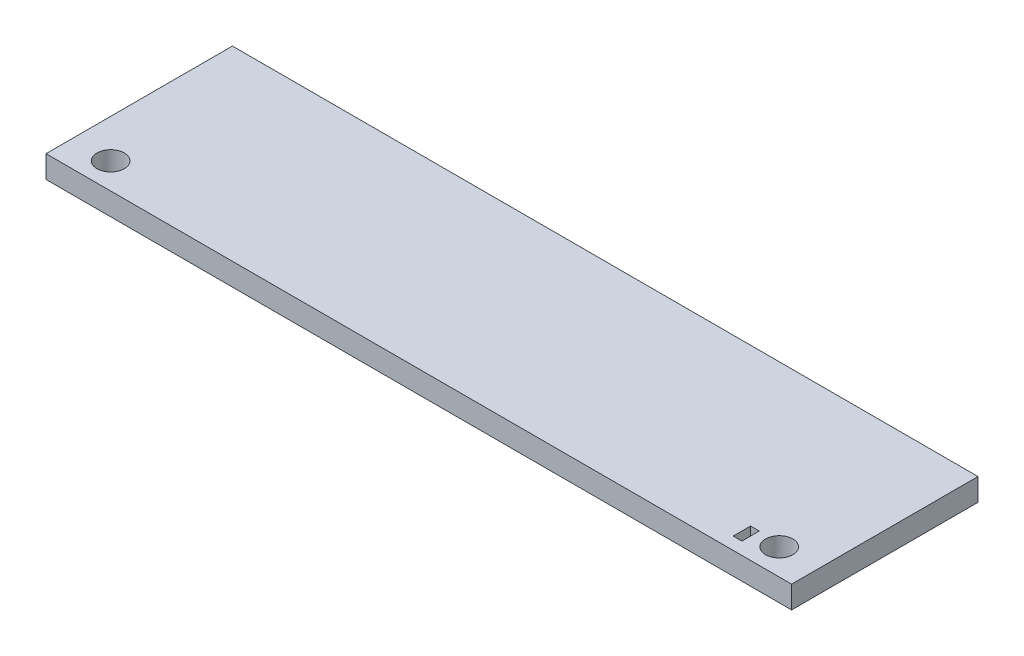
SolidWorks part; units mm, degrees
ref_plane "Plan de face" through (0, 0, 0) normal (0, 0, 1) x (1, 0, 0)
ref_plane "Plan de dessus" through (0, 0, 0) normal (0, 1, 0) x (1, 0, 0)
ref_plane "Plan de droite" through (0, 0, 0) normal (1, 0, 0) x (0, 0, -1)
sketch "Esquisse1" plane through (0, 0, 0) normal (0, 1, 0) x (1, 0, 0)
  line L1 (-300, 75) -> (300, 75)
  line L2 (-300, 75) -> (-300, -75)
  line L3 (-300, -75) -> (300, -75)
  line L4 (300, 75) -> (300, -75)
  line L5 (-300, 75) -> (300, -75) construction
  line L6 (-300, -75) -> (300, 75) construction
  point P0 (0, 0)
  dimension "D1" = 600
  dimension "D2" = 150
extrude "Boss.-Extru.1" add sketch "Esquisse1" along normal blind 18
sketch "Esquisse2" plane through (0, 18, 0) normal (0, 1, 0) x (1, 0, 0)
  line L0 (-300, 75) -> (-300, -75) construction
  line L1 (-300, 55) -> (300, 55)
  line L2 (-300, 55) -> (-300, 35)
  line L3 (-300, 35) -> (300, 35)
  line L4 (300, 55) -> (300, 35)
  line L5 (300, -75) -> (300, 75) construction
  line L6 (300, 75) -> (-300, 75) construction
  dimension "D1" = 20
  dimension "D2" = 20
sketch "Esquisse3" plane through (0, 18, 0) normal (0, 1, 0) x (1, 0, 0)
  line L0 (-238, -75) -> (-238, -33) construction
  line L1 (-300, -75) -> (300, -75) construction
  line L2 (-238, -33) -> (-300, -33) construction
  line L3 (-300, 75) -> (-300, -75) construction
  line L4 (238, -75) -> (238, -33) construction
  line L5 (238, -33) -> (300, -33) construction
  line L6 (300, -75) -> (300, 75) construction
  line L7 (238, -33) -> (300, -75) construction
  line L8 (-238, -33) -> (-300, -75) construction
  circle A0 centre (269, -54) radius 11
  circle A1 centre (-269, -54) radius 11
  dimension "D5" = 22
  dimension "D6" = 22
  dimension "D1" = 62
  dimension "D2" = 42
  dimension "D3" = 62
  dimension "D4" = 42
extrude "Enlèv. mat.-Extru.1" cut sketch "Esquisse3" against normal blind 20
sketch "Esquisse4" plane through (0, 18, 0) normal (0, 1, 0) x (1, 0, 0)
  line L0 (300, -75) -> (300, 75) construction
  line L1 (243, -51) -> (250, -51)
  line L2 (243, -51) -> (243, -65)
  line L3 (243, -65) -> (250, -65)
  line L4 (250, -51) -> (250, -65)
  line L5 (243, -51) -> (250, -65) construction
  line L6 (243, -65) -> (250, -51) construction
  line L7 (-300, -75) -> (300, -75) construction
  point P0 (246.5, -58)
  dimension "D1" = 14
  dimension "D2" = 7
  dimension "D3" = 50
  dimension "D4" = 10
extrude "Enlèv. mat.-Extru.2" cut sketch "Esquisse4" against normal blind 12
